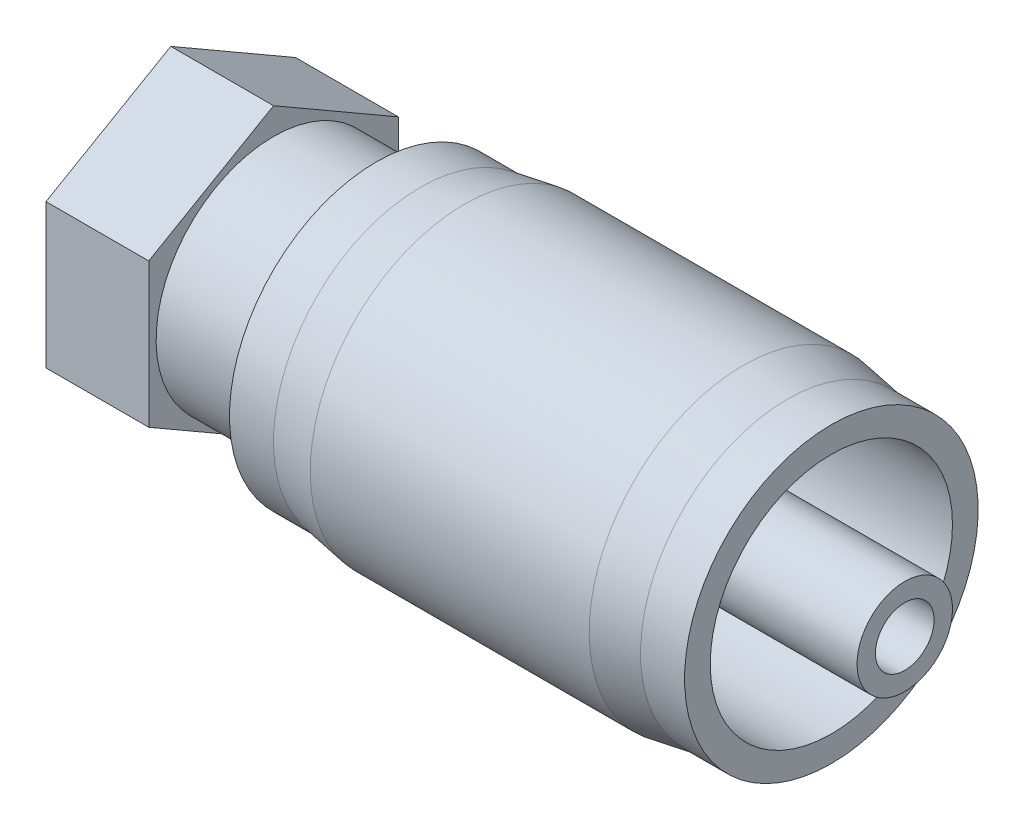
SolidWorks part; units mm, degrees
material "Stahl verzinkt 2"
ref_plane "Vorne" through (0, 0, 0) normal (0, 0, 1) x (1, 0, 0)
ref_plane "Oben" through (0, 0, 0) normal (0, 1, 0) x (1, 0, 0)
ref_plane "Rechts" through (0, 0, 0) normal (1, 0, 0) x (0, 0, -1)
sketch "Skizze1" plane through (0, 0, 0) normal (0, 0, 1) x (1, 0, 0)
  line L0 (92.3902, 0) -> (-26.5606, 0) construction
  line L1 (1, 2) -> (50, 2)
  line L2 (50, 2) -> (50, 3.25)
  line L3 (50, 3.25) -> (24, 3.25)
  line L4 (24, 3.25) -> (24, 8.25)
  line L5 (24, 8.25) -> (45, 8.25)
  line L6 (45, 8.25) -> (45, 10)
  line L7 (39, 10.5) -> (20, 10.5)
  line L8 (17, 10) -> (20, 10.5)
  line L9 (39, 10.5) -> (42, 10)
  line L10 (14, 5.75) -> (14, 10)
  line L11 (14, 10) -> (17, 10)
  line L12 (42, 10) -> (45, 10)
  line L13 (14, 5.75) -> (13, 5.75)
  line L14 (13, 5.75) -> (13, 8)
  line L15 (7, 11) -> (0, 11)
  line L16 (0, 11) -> (0, 5.25)
  line L17 (0, 5.25) -> (8, 5.25)
  line L18 (8, 5.25) -> (8, 4.5)
  line L19 (8, 4.5) -> (1, 4.5)
  line L20 (1, 4.5) -> (1, 2)
  line L23 (7, 11) -> (7, 8)
  line L24 (7, 8) -> (13, 8)
  dimension "D1" = 22
  dimension "D3" = 10.5
  dimension "D4" = 4
  dimension "D5" = 9
  dimension "D6" = 1
  dimension "D7" = 8
  dimension "D8" = 1
  dimension "D9" = 11.5
  dimension "D10" = 6
  dimension "D11" = 3
  dimension "D12" = 20
  dimension "D13" = 21
  dimension "D14" = 16.5
  dimension "D15" = 31
  dimension "D16" = 6.5
  dimension "D17" = 5
  dimension "D18" = 50
  dimension "D19" = 21
  dimension "D22" = 16
  dimension "D23" = 6
revolve "Rotation3" add sketch "Skizze1" angle 360 about L0
cosmetic thread "Gewindedarstellung1" parameters "D2"=12
sketch "Skizze2" plane through (0, 0, 0) normal (-1, 0, 0) x (0, 0, 1)
  line L1 (-8.5, -4.9075) -> (0, -9.815)
  line L2 (0, -9.815) -> (8.5, -4.9075)
  line L3 (8.5, -4.9075) -> (8.5, 4.9075)
  line L4 (8.5, 4.9075) -> (0, 9.815)
  line L5 (0, 9.815) -> (-8.5, 4.9075)
  line L6 (-8.5, 4.9075) -> (-8.5, -4.9075)
  circle A0 centre (0, 0) radius 8.5 construction
  circle A1 centre (0, 0) radius 11
  circle A2 centre (0, 0) radius 11 construction
  dimension "D1" = 17
extrude "Schnitt-Linear austragen1" cut sketch "Skizze2" against normal up to next
other "APunkt1" parameters "Durchmesser"=14.3, "Stumpflänge"=30
ref_axis "Achse1" through (34, 0, 0) along (-1, 0, 0)
